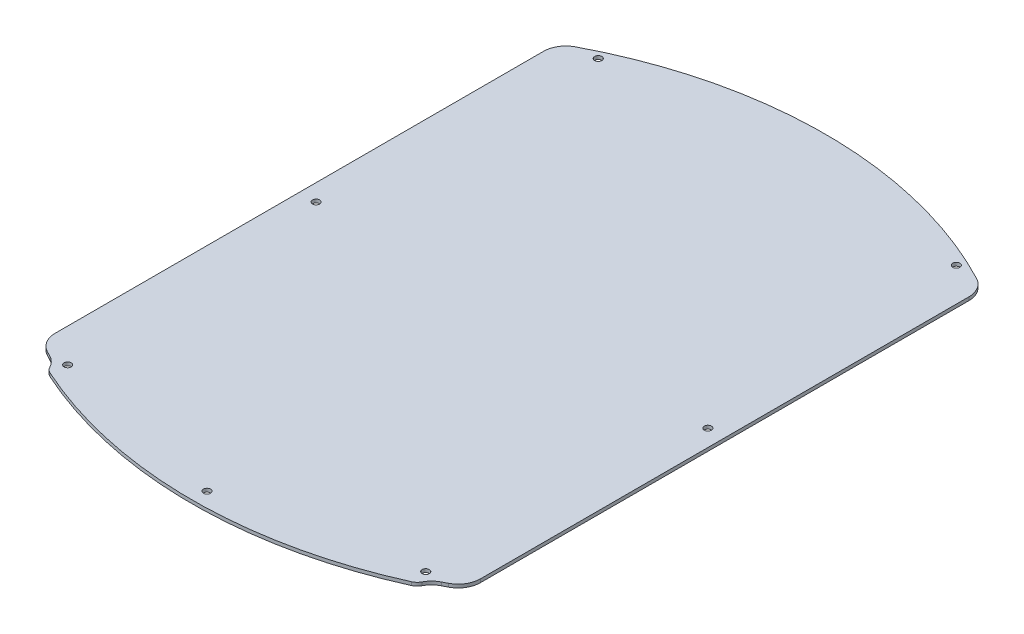
SolidWorks part; units mm, degrees
material "1.0037 (S235JR)"
ref_plane "Front Plane" through (0, 0, 0) normal (0, 0, 1) x (1, 0, 0)
ref_plane "Top Plane" through (0, 0, 0) normal (0, 1, 0) x (1, 0, 0)
ref_plane "Right Plane" through (0, 0, 0) normal (1, 0, 0) x (0, 0, -1)
sketch "Sketch1" plane through (0, 0, 0) normal (0, 1, 0) x (1, 0, 0)
  line L0 (0, -140) -> (0, -115) construction
  line L1 (95, -115) -> (-95, -115) construction
  line L2 (95, -115) -> (95, 115)
  line L3 (95, 115) -> (-95, 115) construction
  line L4 (-95, -115) -> (-95, 115)
  line L5 (95, -115) -> (-95, 115) construction
  line L6 (95, 115) -> (-95, -115) construction
  line L7 (0, 140) -> (0, 115) construction
  arc A0 (-95, -115) -> (95, -115) centre (0, 53) ccw
  arc A1 (-95, 115) -> (95, 115) centre (0, -53) cw
  point P0 (0, 0)
  dimension "D3" = 25
  dimension "D1" = 190
  dimension "D2" = 230
base flange "Base-Flange1" sketch "Sketch1" thickness 1.5 reverse thickness direction no parameters "D1"=2
sketch "Sketch2" plane through (0, 0, 0) normal (0, 1, 0) x (1, 0, 0)
  line L0 (-82.5, -124.7913) -> (-82.5, -121.4785)
  line L9 (82.5, -124.7913) -> (82.5, -121.4785)
  arc A0 (-95, -115) -> (95, -115) centre (0, 53) ccw construction
  arc A5 (-82.5, -121.4785) -> (82.5, -121.4785) centre (0, 53) ccw
  arc A8 (-96.4767, -117.6114) -> (96.4767, -117.6114) centre (0, 53) ccw
  arc A9 (-82.5, -124.7913) -> (82.5, -124.7913) centre (0, 53) ccw
  point P7 (0, -140)
  dimension "D2" = 165
  dimension "D1" = 3
base flange "Tab1" sketch "Sketch2" thickness 1.5 reverse thickness direction no parameters "D1"=2
fillet "Fillet1" radius 10 6 edges at (-95, -0.75, 115) (95, -0.75, 115) (-82.5, -0.75, 121.4785) (82.5, -0.75, 121.4785) (-95, -0.75, -115) (95, -0.75, -115)
fillet "Fillet2" radius 5 2 edges at (82.5, -0.75, 124.7913) (-82.5, -0.75, 124.7913)
sketch "Sketch9" plane through (0, 0, 0) normal (0, 1, 0) x (1, 0, 0)
  circle A0 centre (-79.9805, 118.5187) radius 1.6 construction
  circle A1 centre (-79.9805, 118.5187) radius 1.6
  circle A2 centre (79.9805, 118.5187) radius 1.6 construction
  circle A3 centre (79.9805, 118.5187) radius 1.6
  circle A4 centre (87.5, 0) radius 1.25 construction
  circle A5 centre (87.5, 0) radius 1.25 construction
  circle A6 centre (-87.5, 0) radius 1.25 construction
  circle A7 centre (-87.5, 0) radius 1.25 construction
  circle A8 centre (-79.9805, -118.5187) radius 1.6 construction
  circle A9 centre (-79.9805, -118.5187) radius 1.6
  circle A10 centre (0, -136.25) radius 1.6 construction
  circle A11 centre (0, -136.25) radius 1.6
  circle A12 centre (79.9805, -118.5187) radius 1.6 construction
  circle A13 centre (79.9805, -118.5187) radius 1.6
  circle A14 centre (87.5, 0) radius 1.6
  circle A15 centre (-87.5, 0) radius 1.6
  dimension "D1" = 3.2
extrude "Cut-Extrude1" cut sketch "Sketch9" against normal through all normal cut yes
sketch "Bend-Lines1" [suppressed] plane through (0, 0, 0) normal (0, 1, 0) x (1, 0, 0)
sketch "Bounding-Box1" [suppressed] plane through (0, 0, 0) normal (0, 1, 0) x (1, 0, 0)
sheet metal parameters "Sheet-Metal1" thickness 1.5 parameters "D1"=2
flat pattern "Flat-Pattern1" [suppressed]
sketch "Bend-Lines2" plane through (0, 0, 0) normal (0, 1, 0) x (1, 0, 0)
sketch3d "Bounding-Box2" [suppressed]
  line L0 (-95, 64.375, 0) -> (-95, -235.625, 0) construction
  line L1 (95, 64.375, 0) -> (95, -235.625, 0) construction
  line L2 (-95, 64.375, 0) -> (95, 64.375, 0) construction
  line L3 (-95, -235.625, 0) -> (95, -235.625, 0) construction
sheet metal parameters "Sheet-Metal2" thickness 1.5 parameters "D1"=2
flat pattern "Flat-Pattern2"
sketch "Bend-Lines3" plane through (0, 0, 0) normal (0, 1, 0) x (1, 0, 0)
sketch3d "Bounding-Box3" [suppressed]
  line L0 (-95, -90, 0) -> (-95, 193, 0) construction
  line L1 (95, -90, 0) -> (95, 193, 0) construction
  line L2 (-95, -90, 0) -> (95, -90, 0) construction
  line L3 (-95, 193, 0) -> (95, 193, 0) construction
sheet metal parameters "Sheet-Metal7" thickness 1.5 parameters "D1"=2
flat pattern "Flat-Pattern2"
sketch "Bend-Lines3" plane through (0, 0, 0) normal (0, 1, 0) x (1, 0, 0)
sketch3d "Bounding-Box3" [suppressed]
  line L0 (-95, -90, 0) -> (-95, 193, 0) construction
  line L1 (95, -90, 0) -> (95, 193, 0) construction
  line L2 (-95, -90, 0) -> (95, -90, 0) construction
  line L3 (-95, 193, 0) -> (95, 193, 0) construction
